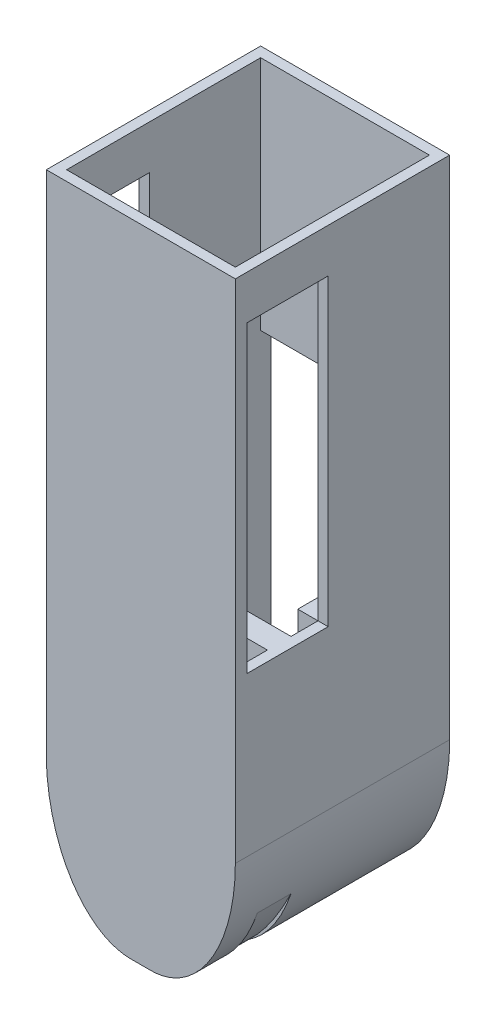
SolidWorks part; units mm, degrees
material "Aleación 1060"
ref_plane "Alzado" through (0, 0, 0) normal (0, 0, 1) x (1, 0, 0)
ref_plane "Planta" through (0, 0, 0) normal (0, 1, 0) x (1, 0, 0)
ref_plane "Vista lateral" through (0, 0, 0) normal (1, 0, 0) x (0, 0, -1)
sketch "Croquis2" plane through (0, 0, 0) normal (0, 0, 1) x (1, 0, 0)
  line L1 (-28, -95) -> (28, -95)
  line L2 (-28, -95) -> (-28, 95)
  line L3 (-28, 95) -> (28, 95)
  line L4 (28, -95) -> (28, 95)
  line L5 (-28, -95) -> (28, 95) construction
  line L6 (-28, 95) -> (28, -95) construction
  point P0 (0, 0)
  dimension "D1" = 56
  dimension "D2" = 190
extrude "Saliente-Extruir1" add sketch "Croquis2" along normal blind 63.5
fillet "Redondeo1" radius 40 2 edges at (-28, -95, 31.75) (28, -95, 31.75) second distance 25 first distance on face at (-28, 0, 31.75) first distance on face at (28, 0, 31.75)
shell "Vaciado2" thickness 3 removed face at (0, 95, 31.75)
sketch "Croquis9" plane through (0, 0, 60.5) normal (0, 0, -1) x (-1, 0, 0)
  line L1 (-28, 95) -> (28, 95) construction
  line L2 (28, 95) -> (28, -55) construction
  circle A0 centre (0, 70) radius 4
  dimension "D1" = 8
  dimension "D2" = 25
  dimension "D3" = 28
sketch "Croquis10" plane through (28, 0, 0) normal (1, 0, 0) x (0, 0, -1)
  line L0 (-63.5, 95) -> (0, 95) construction
  line L1 (-60, 82) -> (-36, 82)
  line L2 (-60, 82) -> (-60, -8)
  line L3 (-60, -8) -> (-36, -8)
  line L4 (-36, 82) -> (-36, -8)
  line L6 (0, -55) -> (0, 95) construction
  dimension "D1" = 13
  dimension "D2" = 36
  dimension "D3" = 24
  dimension "D4" = 90
extrude "Cortar-Extruir1" cut sketch "Croquis10" against normal blind 129
sketch "Croquis12" plane through (0, -92, 0) normal (0, 1, 0) x (1, 0, 0)
  line L0 (25, -60.5) -> (25, -3) construction
  line L1 (25, -51) -> (-25, -51)
  line L2 (25, -51) -> (25, -44)
  line L3 (25, -44) -> (-25, -44)
  line L4 (-25, -51) -> (-25, -44)
  line L5 (-25, -3) -> (-25, -60.5) construction
  line L6 (25, -60.5) -> (-25, -60.5) construction
  dimension "D1" = 9.5
  dimension "D2" = 7
extrude "Saliente-Extruir2" add sketch "Croquis12" along normal blind 84
sketch "Croquis13" plane through (0, -8, 0) normal (0, 1, 0) x (1, 0, 0)
  line L0 (25, -44) -> (-25, -44) construction
  line L1 (-4, -51.0316) -> (4, -51.0316)
  line L2 (-4, -51.0316) -> (-4, -44)
  line L3 (-4, -44) -> (4, -44)
  line L4 (4, -51.0316) -> (4, -44)
  line L5 (-4, -51.0316) -> (4, -44) construction
  line L6 (-4, -44) -> (4, -51.0316) construction
  line L7 (28, -63.5) -> (28, 0) construction
  point P0 (0, -47.5158)
  dimension "D2" = 0
  dimension "D3" = 8
  dimension "D4" = 28
extrude "Cortar-Extruir2" cut sketch "Croquis13" against normal blind 84
sketch "Croquis14" plane through (0, -95, 0) normal (0, -1, 0) x (1, 0, 0)
  circle A0 centre (0, 28) radius 5
  dimension "D1" = 10
extrude "Cortar-Extruir3" cut sketch "Croquis14" against normal blind 84
sketch "Croquis15" plane through (0, 0, 0) normal (0, 0, -1) x (-1, 0, 0)
  line L0 (-28, 95) -> (28, 95) construction
  line L1 (-25, -65) -> (25, -65)
  line L2 (-25, -65) -> (-25, 25)
  line L3 (-25, 25) -> (25, 25)
  line L4 (25, -65) -> (25, 25)
  line L5 (3, -95) -> (-3, -95) construction
  line L6 (28, 95) -> (28, -55) construction
  line L7 (-28, -55) -> (-28, 95) construction
  dimension "D1" = 70
  dimension "D2" = 30
  dimension "D3" = 3
  dimension "D4" = 3
extrude "Cortar-Extruir4" cut sketch "Croquis15" against normal blind 3
sketch "Croquis17" plane through (0, 0, 44) normal (0, 0, -1) x (-1, 0, 0)
  line L0 (-25, -73.9989) -> (-25, -92)
  line L1 (-25, -92) -> (-12.4992, -92)
  line L2 (12.4992, -92) -> (25, -92)
  line L3 (25, -92) -> (25, -73.9989)
  spline S0 degree 2 poles (12.4992, -92) (22.6101, -82.7973) (25, -73.9989) knots 0 0 0 0.715272 0.715272 0.715272
  spline S1 degree 2 poles (-25, -73.9989) (-19.1549, -85.8237) (-12.4992, -92) knots 0 0 0 0.69519 0.69519 0.69519
extrude "Cortar-Extruir5" cut sketch "Croquis17" against normal blind 10
sketch "Croquis18" plane through (-25, 0, 0) normal (1, 0, 0) x (0, 0, -1)
  line L1 (-21, -65) -> (-36, -65)
  line L2 (-21, -65) -> (-21, -8)
  line L3 (-21, -8) -> (-36, -8)
  line L4 (-36, -65) -> (-36, -8)
  dimension "D1" = 15
extrude "Saliente-Extruir4" add sketch "Croquis18" along normal blind 6 separate body
sketch "Croquis19" plane through (25, 0, 0) normal (-1, 0, 0) x (0, 0, 1)
  line L1 (21, -65) -> (36, -65)
  line L2 (21, -65) -> (21, -8)
  line L3 (21, -8) -> (36, -8)
  line L4 (36, -65) -> (36, -8)
  dimension "D1" = 15
extrude "Saliente-Extruir5" add sketch "Croquis19" along normal blind 6 separate body
